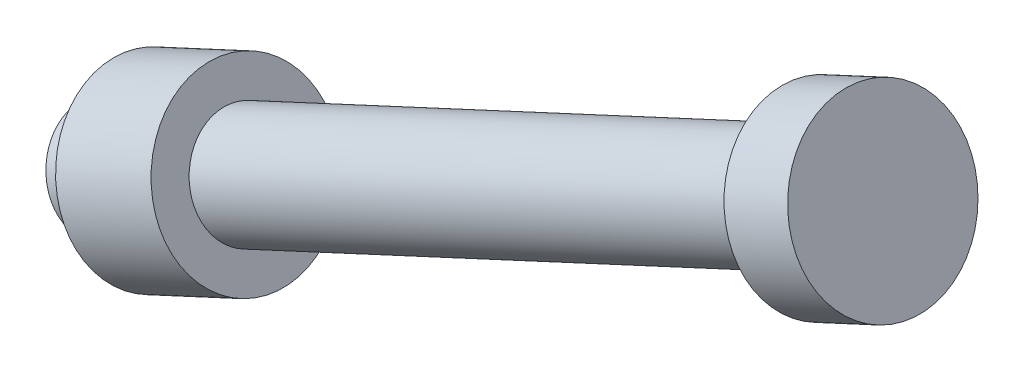
SolidWorks part; units mm, degrees
ref_plane "Alzado" through (0, 0, 0) normal (0, 0, 1) x (1, 0, 0)
ref_plane "Planta" through (0, 0, 0) normal (0, 1, 0) x (1, 0, 0)
ref_plane "Vista lateral" through (0, 0, 0) normal (1, 0, 0) x (0, 0, -1)
sketch3d "Sk_Cabeza"
  line L0 (436.5934, 392.8864, 0) -> (440.2217, 394.5702, 0)
  dimension "D1" = 4
sweep "Cabeza" add path "Sk_Cabeza" circular profile diameter 10 parameters "D3"=10
sketch3d "Sk_Vastago"
  line L0 (395.775, 373.9428, 0) -> (436.5934, 392.8864, 0)
  dimension "D1" = 45
sweep "Vastago" add path "Sk_Vastago" circular profile diameter 6 parameters "D3"=6
sketch3d "Sk_Tuerca"
  line L0 (398.4962, 375.2057, 0) -> (403.9387, 377.7315, 0)
  dimension "D1" = 6
sweep "Tuerca" add path "Sk_Tuerca" circular profile diameter 10 parameters "D3"=10
